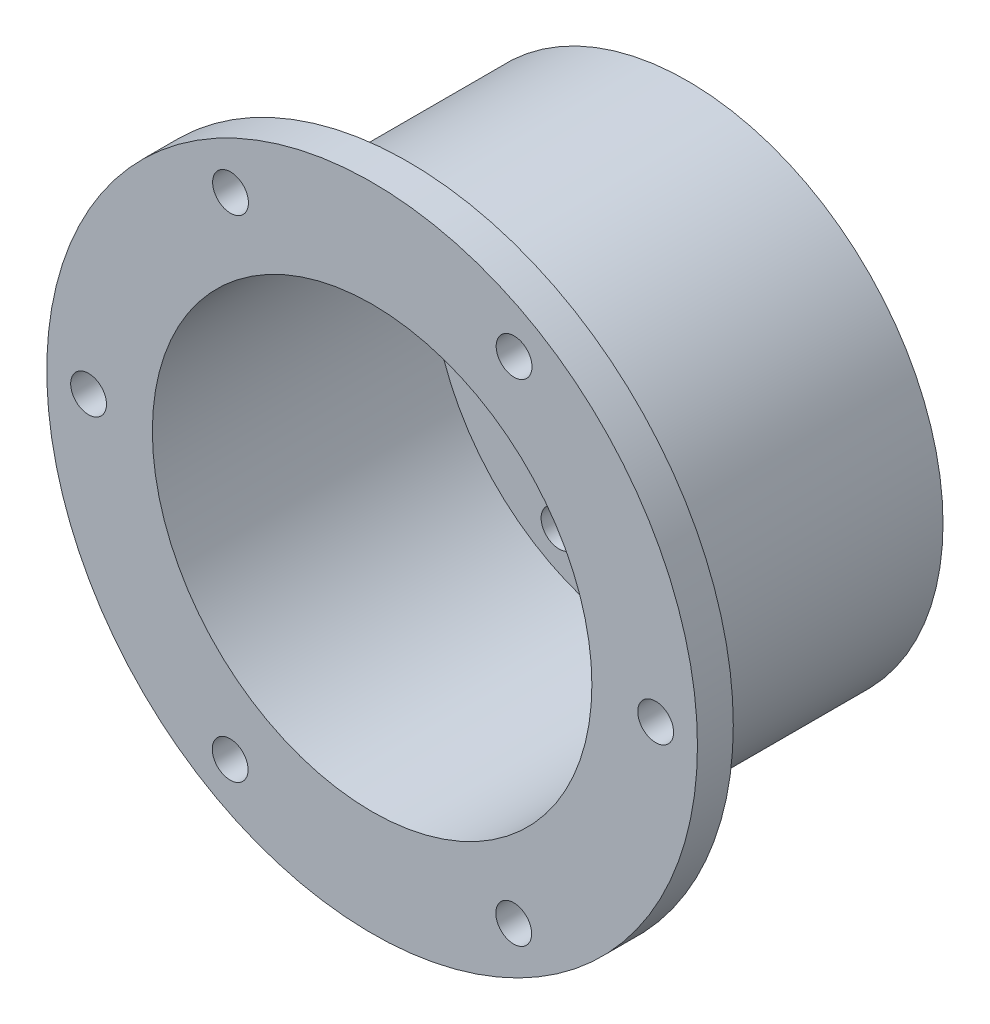
SolidWorks part; units mm, degrees
material "Resina de melamina"
ref_plane "Alzado" through (0, 0, 0) normal (0, 0, 1) x (1, 0, 0)
ref_plane "Planta" through (0, 0, 0) normal (0, 1, 0) x (1, 0, 0)
ref_plane "Vista lateral" through (0, 0, 0) normal (1, 0, 0) x (0, 0, -1)
sketch "Croquis1" plane through (0, 0, 0) normal (0, 0, 1) x (1, 0, 0)
  circle A0 centre (0, 0) radius 18.4
  circle A1 centre (0, 0) radius 21.4
  dimension "D1" = 36.8
  dimension "D2" = 42.8
extrude "Saliente-Extruir1" add sketch "Croquis1" along normal blind 26.4
sketch "Croquis2" plane through (0, 0, 0) normal (0, 0, -1) x (-1, 0, 0)
  circle A0 centre (0, 0) radius 18.4
extrude "Saliente-Extruir2" add sketch "Croquis2" against normal blind 3
sketch "Croquis3" plane through (0, 0, 26.4) normal (0, 0, 1) x (1, 0, 0)
  circle A0 centre (0, 0) radius 21.4
  circle A1 centre (0, 0) radius 27.24
  dimension "D1" = 54.48
extrude "Saliente-Extruir3" add sketch "Croquis3" against normal blind 3
sketch "Croquis4" plane through (0, 0, 0) normal (0, 0, -1) x (-1, 0, 0)
  line L0 (0, 0) -> (0, -7) construction
  line L1 (-13, 0) -> (-14, 0) construction
  line L2 (-14, 0) -> (-17, 0) construction
  circle A0 centre (0, -7) radius 6
  circle A9 centre (-15.5, 0) radius 1.5
  circle A10 centre (-7.75, 13.4234) radius 1.5
  circle A11 centre (7.75, 13.4234) radius 1.5
  circle A12 centre (15.5, 0) radius 1.5
  circle A13 centre (7.75, -13.4234) radius 1.5
  circle A14 centre (-7.75, -13.4234) radius 1.5
  dimension "D2" = 12
  dimension "D1" = 7
  dimension "D3" = 1
  dimension "D4" = 3
  dimension "D5" = 6
extrude "Cortar-Extruir1" cut sketch "Croquis4" against normal blind 3
sketch "Croquis6" plane through (0, 0, 26.4) normal (0, 0, 1) x (1, 0, 0)
  line L0 (0, 0) -> (-7.75, 13.4234) construction
  line L1 (-7.75, 13.4234) -> (-9.1877, 15.942) construction
  line L2 (-9.1877, 15.942) -> (-13.6018, 23.601) construction
  line L3 (-13.6018, 23.601) -> (-11.8541, 20.5686) construction
  circle A0 centre (0, 0) radius 18.4 construction
  circle A9 centre (0, 0) radius 27.24 construction
  circle A10 centre (-11.8541, 20.5686) radius 1.5
  circle A11 centre (11.8859, 20.5503) radius 1.5
  circle A12 centre (23.74, -0.0183) radius 1.5
  circle A13 centre (11.8541, -20.5686) radius 1.5
  circle A14 centre (-11.8859, -20.5503) radius 1.5
  circle A15 centre (-23.74, 0.0183) radius 1.5
  dimension "D1" = 3.5
  dimension "D2" = 3
  dimension "D3" = 6
extrude "Cortar-Extruir2" cut sketch "Croquis6" against normal blind 3
